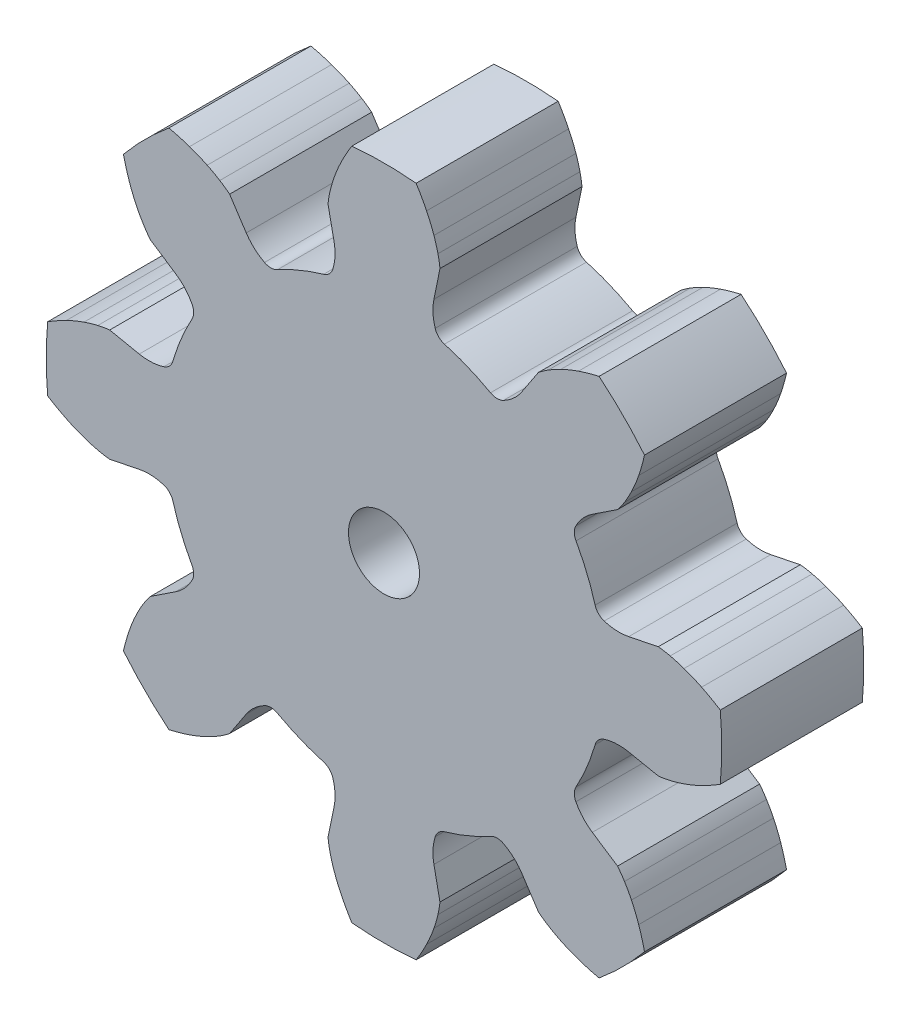
SolidWorks part; units mm, degrees
ref_plane "Front Plane" through (0, 0, 0) normal (0, 0, 1) x (1, 0, 0)
ref_plane "Top Plane" through (0, 0, 0) normal (0, 1, 0) x (1, 0, 0)
ref_plane "Right Plane" through (0, 0, 0) normal (1, 0, 0) x (0, 0, -1)
sketch "Model" plane through (0, 0, 0) normal (0, 0, 1) x (1, 0, 0)
  line L0 (10.9417, -2.2327) -> (12.2644, -2.5026)
  line L1 (12.2644, 2.5026) -> (10.9417, 2.2327)
  line L2 (9.3157, 6.1582) -> (10.4419, 6.9027)
  line L3 (6.9027, 10.4419) -> (6.1582, 9.3157)
  line L4 (2.2327, 10.9417) -> (2.5026, 12.2644)
  line L5 (-2.5026, 12.2644) -> (-2.2327, 10.9417)
  line L6 (-6.1582, 9.3157) -> (-6.9027, 10.4419)
  line L7 (-10.4419, 6.9027) -> (-9.3157, 6.1582)
  line L8 (-10.9417, 2.2327) -> (-12.2644, 2.5026)
  line L9 (-12.2644, -2.5026) -> (-10.9417, -2.2327)
  line L10 (-9.3157, -6.1582) -> (-10.4419, -6.9027)
  line L11 (-6.9027, -10.4419) -> (-6.1582, -9.3157)
  line L12 (-2.2327, -10.9417) -> (-2.5026, -12.2644)
  line L13 (2.5026, -12.2644) -> (2.2327, -10.9417)
  line L14 (6.1582, -9.3157) -> (6.9027, -10.4419)
  line L15 (10.4419, -6.9027) -> (9.3157, -6.1582)
  arc A1 (9.072, -3.7577) -> (9.44, -2.7033) centre (0, 0) ccw
  arc A2 (9.8442, -2.2889) -> (9.44, -2.7033) centre (10.0267, -2.8713) ccw
  arc A3 (10.9417, -2.2327) -> (9.8442, -2.2889) centre (10.502, -4.3879) ccw
  arc A4 (12.2644, -2.5026) -> (12.7952, -2.4127) centre (11.8124, 1.7812) ccw
  arc A5 (12.7952, -2.4127) -> (13.4129, -2.2334) centre (11.3922, 3.5743) ccw
  arc A6 (13.4129, -2.2334) -> (14.2001, -1.9047) centre (11.1046, 4.4008) ccw
  arc A7 (14.2001, -1.9047) -> (15.0358, -1.4368) centre (10.2968, 6.0465) ccw
  arc A8 (15.0358, -1.4368) -> (15.0358, 1.4368) centre (0, 0) ccw
  arc A9 (15.0358, 1.4368) -> (14.2001, 1.9047) centre (10.2968, -6.0465) ccw
  arc A10 (14.2001, 1.9047) -> (13.4129, 2.2334) centre (11.1046, -4.4008) ccw
  arc A11 (13.4129, 2.2334) -> (12.7952, 2.4127) centre (11.3922, -3.5743) ccw
  arc A12 (12.7952, 2.4127) -> (12.2644, 2.5026) centre (11.8124, -1.7812) ccw
  arc A13 (9.8442, 2.2889) -> (10.9417, 2.2327) centre (10.502, 4.3879) ccw
  arc A14 (9.44, 2.7033) -> (9.8442, 2.2889) centre (10.0267, 2.8713) ccw
  arc A15 (9.44, 2.7033) -> (8.5866, 4.7635) centre (0, 0) ccw
  arc A16 (8.5794, 5.3424) -> (8.5866, 4.7635) centre (9.1203, 5.0596) ccw
  arc A17 (9.3157, 6.1582) -> (8.5794, 5.3424) centre (10.5287, 4.3233) ccw
  arc A18 (10.4419, 6.9027) -> (10.7537, 7.3415) centre (7.0931, 9.6121) ccw
  arc A19 (10.7537, 7.3415) -> (11.0637, 7.9051) centre (5.5281, 10.5829) ccw
  arc A20 (11.0637, 7.9051) -> (11.3878, 8.6941) centre (4.7403, 10.964) ccw
  arc A21 (11.3878, 8.6941) -> (11.6479, 9.616) centre (3.0054, 11.5564) ccw
  arc A22 (11.6479, 9.616) -> (9.616, 11.6479) centre (0, 0) ccw
  arc A23 (9.616, 11.6479) -> (8.6941, 11.3878) centre (11.5564, 3.0054) ccw
  arc A24 (8.6941, 11.3878) -> (7.9051, 11.0637) centre (10.964, 4.7403) ccw
  arc A25 (7.9051, 11.0637) -> (7.3415, 10.7537) centre (10.5829, 5.5281) ccw
  arc A26 (7.3415, 10.7537) -> (6.9027, 10.4419) centre (9.6121, 7.0931) ccw
  arc A27 (5.3424, 8.5794) -> (6.1582, 9.3157) centre (4.3233, 10.5287) ccw
  arc A28 (4.7635, 8.5866) -> (5.3424, 8.5794) centre (5.0596, 9.1203) ccw
  arc A29 (4.7635, 8.5866) -> (2.7033, 9.44) centre (0, 0) ccw
  arc A30 (2.2889, 9.8442) -> (2.7033, 9.44) centre (2.8713, 10.0267) ccw
  arc A31 (2.2327, 10.9417) -> (2.2889, 9.8442) centre (4.3879, 10.502) ccw
  arc A32 (2.5026, 12.2644) -> (2.4127, 12.7952) centre (-1.7812, 11.8124) ccw
  arc A33 (2.4127, 12.7952) -> (2.2334, 13.4129) centre (-3.5743, 11.3922) ccw
  arc A34 (2.2334, 13.4129) -> (1.9047, 14.2001) centre (-4.4008, 11.1046) ccw
  arc A35 (1.9047, 14.2001) -> (1.4368, 15.0358) centre (-6.0465, 10.2968) ccw
  arc A36 (1.4368, 15.0358) -> (-1.4368, 15.0358) centre (0, 0) ccw
  arc A37 (-1.4368, 15.0358) -> (-1.9047, 14.2001) centre (6.0465, 10.2968) ccw
  arc A38 (-1.9047, 14.2001) -> (-2.2334, 13.4129) centre (4.4008, 11.1046) ccw
  arc A39 (-2.2334, 13.4129) -> (-2.4127, 12.7952) centre (3.5743, 11.3922) ccw
  arc A40 (-2.4127, 12.7952) -> (-2.5026, 12.2644) centre (1.7812, 11.8124) ccw
  arc A41 (-2.2889, 9.8442) -> (-2.2327, 10.9417) centre (-4.3879, 10.502) ccw
  arc A42 (-2.7033, 9.44) -> (-2.2889, 9.8442) centre (-2.8713, 10.0267) ccw
  arc A43 (-2.7033, 9.44) -> (-4.7635, 8.5866) centre (0, 0) ccw
  arc A44 (-5.3424, 8.5794) -> (-4.7635, 8.5866) centre (-5.0596, 9.1203) ccw
  arc A45 (-6.1582, 9.3157) -> (-5.3424, 8.5794) centre (-4.3233, 10.5287) ccw
  arc A46 (-6.9027, 10.4419) -> (-7.3415, 10.7537) centre (-9.6121, 7.0931) ccw
  arc A47 (-7.3415, 10.7537) -> (-7.9051, 11.0637) centre (-10.5829, 5.5281) ccw
  arc A48 (-7.9051, 11.0637) -> (-8.6941, 11.3878) centre (-10.964, 4.7403) ccw
  arc A49 (-8.6941, 11.3878) -> (-9.616, 11.6479) centre (-11.5564, 3.0054) ccw
  arc A50 (-9.616, 11.6479) -> (-11.6479, 9.616) centre (0, 0) ccw
  arc A51 (-11.6479, 9.616) -> (-11.3878, 8.6941) centre (-3.0054, 11.5564) ccw
  arc A52 (-11.3878, 8.6941) -> (-11.0637, 7.9051) centre (-4.7403, 10.964) ccw
  arc A53 (-11.0637, 7.9051) -> (-10.7537, 7.3415) centre (-5.5281, 10.5829) ccw
  arc A54 (-10.7537, 7.3415) -> (-10.4419, 6.9027) centre (-7.0931, 9.6121) ccw
  arc A55 (-8.5794, 5.3424) -> (-9.3157, 6.1582) centre (-10.5287, 4.3233) ccw
  arc A56 (-8.5866, 4.7635) -> (-8.5794, 5.3424) centre (-9.1203, 5.0596) ccw
  arc A57 (-8.5866, 4.7635) -> (-9.44, 2.7033) centre (0, 0) ccw
  arc A58 (-9.8442, 2.2889) -> (-9.44, 2.7033) centre (-10.0267, 2.8713) ccw
  arc A59 (-10.9417, 2.2327) -> (-9.8442, 2.2889) centre (-10.502, 4.3879) ccw
  arc A60 (-12.2644, 2.5026) -> (-12.7952, 2.4127) centre (-11.8124, -1.7812) ccw
  arc A61 (-12.7952, 2.4127) -> (-13.4129, 2.2334) centre (-11.3922, -3.5743) ccw
  arc A62 (-13.4129, 2.2334) -> (-14.2001, 1.9047) centre (-11.1046, -4.4008) ccw
  arc A63 (-14.2001, 1.9047) -> (-15.0358, 1.4368) centre (-10.2968, -6.0465) ccw
  arc A64 (-15.0358, 1.4368) -> (-15.0358, -1.4368) centre (0, 0) ccw
  arc A65 (-15.0358, -1.4368) -> (-14.2001, -1.9047) centre (-10.2968, 6.0465) ccw
  arc A66 (-14.2001, -1.9047) -> (-13.4129, -2.2334) centre (-11.1046, 4.4008) ccw
  arc A67 (-13.4129, -2.2334) -> (-12.7952, -2.4127) centre (-11.3922, 3.5743) ccw
  arc A68 (-12.7952, -2.4127) -> (-12.2644, -2.5026) centre (-11.8124, 1.7812) ccw
  arc A69 (-9.8442, -2.2889) -> (-10.9417, -2.2327) centre (-10.502, -4.3879) ccw
  arc A70 (-9.44, -2.7033) -> (-9.8442, -2.2889) centre (-10.0267, -2.8713) ccw
  arc A71 (-9.44, -2.7033) -> (-8.5866, -4.7635) centre (0, 0) ccw
  arc A72 (-8.5794, -5.3424) -> (-8.5866, -4.7635) centre (-9.1203, -5.0596) ccw
  arc A73 (-9.3157, -6.1582) -> (-8.5794, -5.3424) centre (-10.5287, -4.3233) ccw
  arc A74 (-10.4419, -6.9027) -> (-10.7537, -7.3415) centre (-7.0931, -9.6121) ccw
  arc A75 (-10.7537, -7.3415) -> (-11.0637, -7.9051) centre (-5.5281, -10.5829) ccw
  arc A76 (-11.0637, -7.9051) -> (-11.3878, -8.6941) centre (-4.7403, -10.964) ccw
  arc A77 (-11.3878, -8.6941) -> (-11.6479, -9.616) centre (-3.0054, -11.5564) ccw
  arc A78 (-11.6479, -9.616) -> (-9.616, -11.6479) centre (0, 0) ccw
  arc A79 (-9.616, -11.6479) -> (-8.6941, -11.3878) centre (-11.5564, -3.0054) ccw
  arc A80 (-8.6941, -11.3878) -> (-7.9051, -11.0637) centre (-10.964, -4.7403) ccw
  arc A81 (-7.9051, -11.0637) -> (-7.3415, -10.7537) centre (-10.5829, -5.5281) ccw
  arc A82 (-7.3415, -10.7537) -> (-6.9027, -10.4419) centre (-9.6121, -7.0931) ccw
  arc A83 (-5.3424, -8.5794) -> (-6.1582, -9.3157) centre (-4.3233, -10.5287) ccw
  arc A84 (-4.7635, -8.5866) -> (-5.3424, -8.5794) centre (-5.0596, -9.1203) ccw
  arc A85 (-4.7635, -8.5866) -> (-2.7033, -9.44) centre (0, 0) ccw
  arc A86 (-2.2889, -9.8442) -> (-2.7033, -9.44) centre (-2.8713, -10.0267) ccw
  arc A87 (-2.2327, -10.9417) -> (-2.2889, -9.8442) centre (-4.3879, -10.502) ccw
  arc A88 (-2.5026, -12.2644) -> (-2.4127, -12.7952) centre (1.7812, -11.8124) ccw
  arc A89 (-2.4127, -12.7952) -> (-2.2334, -13.4129) centre (3.5743, -11.3922) ccw
  arc A90 (-2.2334, -13.4129) -> (-1.9047, -14.2001) centre (4.4008, -11.1046) ccw
  arc A91 (-1.9047, -14.2001) -> (-1.4368, -15.0358) centre (6.0465, -10.2968) ccw
  arc A92 (-1.4368, -15.0358) -> (1.4368, -15.0358) centre (0, 0) ccw
  arc A93 (1.4368, -15.0358) -> (1.9047, -14.2001) centre (-6.0465, -10.2968) ccw
  arc A94 (1.9047, -14.2001) -> (2.2334, -13.4129) centre (-4.4008, -11.1046) ccw
  arc A95 (2.2334, -13.4129) -> (2.4127, -12.7952) centre (-3.5743, -11.3922) ccw
  arc A96 (2.4127, -12.7952) -> (2.5026, -12.2644) centre (-1.7812, -11.8124) ccw
  arc A97 (2.2889, -9.8442) -> (2.2327, -10.9417) centre (4.3879, -10.502) ccw
  arc A98 (2.7033, -9.44) -> (2.2889, -9.8442) centre (2.8713, -10.0267) ccw
  arc A99 (2.7033, -9.44) -> (4.7635, -8.5866) centre (0, 0) ccw
  arc A100 (5.3424, -8.5794) -> (4.7635, -8.5866) centre (5.0596, -9.1203) ccw
  arc A101 (6.1582, -9.3157) -> (5.3424, -8.5794) centre (4.3233, -10.5287) ccw
  arc A102 (6.9027, -10.4419) -> (7.3415, -10.7537) centre (9.6121, -7.0931) ccw
  arc A103 (7.3415, -10.7537) -> (7.9051, -11.0637) centre (10.5829, -5.5281) ccw
  arc A104 (7.9051, -11.0637) -> (8.6941, -11.3878) centre (10.964, -4.7403) ccw
  arc A105 (8.6941, -11.3878) -> (9.616, -11.6479) centre (11.5564, -3.0054) ccw
  arc A106 (9.616, -11.6479) -> (11.6479, -9.616) centre (0, 0) ccw
  arc A107 (11.6479, -9.616) -> (11.3878, -8.6941) centre (3.0054, -11.5564) ccw
  arc A108 (11.3878, -8.6941) -> (11.0637, -7.9051) centre (4.7403, -10.964) ccw
  arc A109 (11.0637, -7.9051) -> (10.7537, -7.3415) centre (5.5281, -10.5829) ccw
  arc A110 (10.7537, -7.3415) -> (10.4419, -6.9027) centre (7.0931, -9.6121) ccw
  arc A111 (8.5794, -5.3424) -> (9.3157, -6.1582) centre (10.5287, -4.3233) ccw
  arc A112 (8.5866, -4.7635) -> (8.5794, -5.3424) centre (9.1203, -5.0596) ccw
  arc A113 (8.5866, -4.7635) -> (9.072, -3.7577) centre (0, 0) ccw
extrude "Boss-Extrude1" add sketch "Model" along normal blind 6.35
sketch "Sketch2" plane through (0, 0, 6.35) normal (0, 0, 1) x (1, 0, 0)
  circle A0 centre (0, 0) radius 1.5875
  dimension "D1" = 3.175
extrude "Cut-Extrude1" cut sketch "Sketch2" against normal through all
